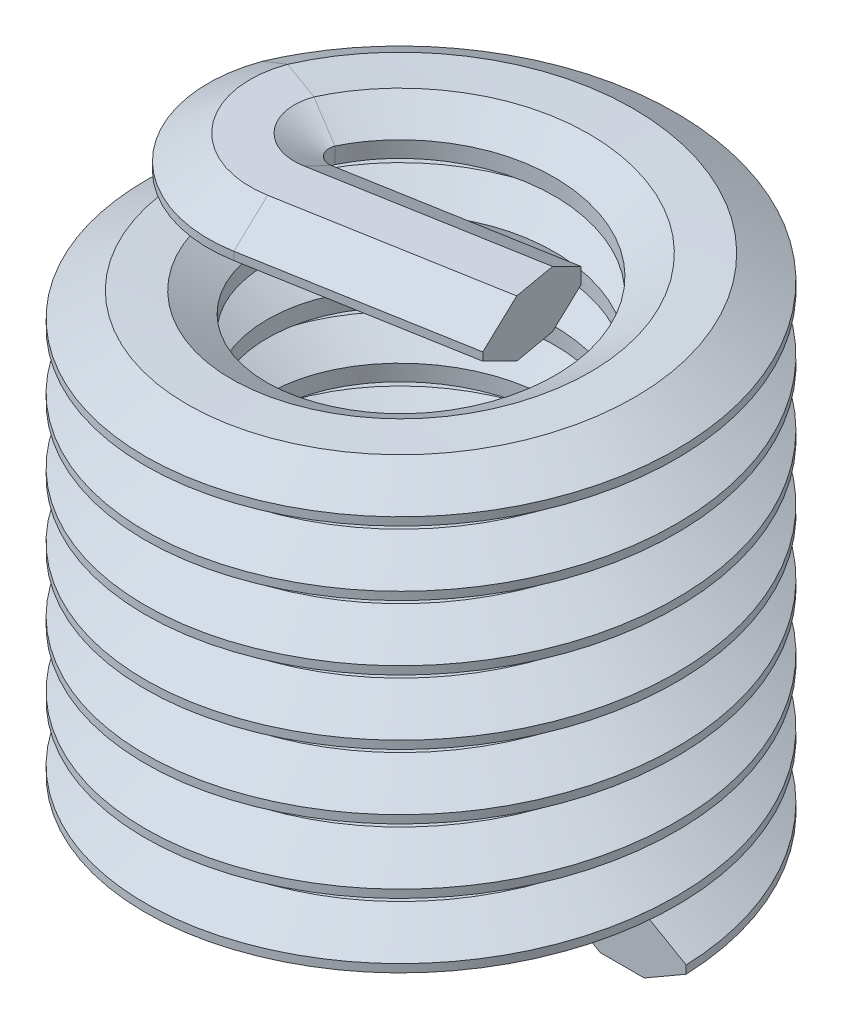
SolidWorks part; units mm, degrees
ref_plane "Front Plane" through (0, 0, 0) normal (0, 0, 1) x (1, 0, 0)
ref_plane "Top Plane" through (0, 0, 0) normal (0, 1, 0) x (1, 0, 0)
ref_plane "Right Plane" through (0, 0, 0) normal (1, 0, 0) x (0, 0, -1)
sketch "Sketch1" plane through (0, 0, 0) normal (0, 0, 1) x (-1, 0, 0)
  line L0 (0, 0) -> (0, 9.525) construction
  line L1 (-0.909, 0) -> (-1.2987, 0.225) construction
  line L2 (-1.509, 0.225) -> (-1.8987, 0) construction
  line L3 (-1.8987, 0) -> (-1.509, -0.225) construction
  line L4 (-1.2987, -0.225) -> (-0.909, 0) construction
  line L5 (-1.2987, -0.225) -> (-1.2987, 0.225) construction
  line L6 (-0.909, 0) -> (0, 0) construction
  line L8 (-1.85, -0.0281) -> (-1.5577, -0.1969)
  line L9 (-1.25, -0.1969) -> (-1.0064, -0.0563)
  line L10 (-0.9577, -0.0281) -> (-0.9577, 0.0281) construction
  line L11 (-1.0064, 0.0563) -> (-1.25, 0.1969)
  line L12 (-1.5577, 0.1969) -> (-1.85, 0.0281)
  line L13 (-0.909, 0) -> (-0.9577, 0) construction
  line L14 (-0.9577, 0) -> (-1.25, 0) construction
  line L15 (-1.5577, 0) -> (-1.85, 0) construction
  line L16 (-1.85, 0) -> (-1.8987, 0) construction
  line L17 (-1.5577, 0.1969) -> (-1.25, 0.1969)
  line L18 (-1.25, 0.1969) -> (-1.25, -0.1969) construction
  line L19 (-1.25, -0.1969) -> (-1.5577, -0.1969)
  line L20 (-1.5577, -0.1969) -> (-1.5577, 0.1969) construction
  line L21 (-1.5577, 0) -> (-1.2987, 0) construction
  line L22 (-1.2987, 0) -> (-1.25, 0) construction
  line L23 (-1.85, 0.225) -> (-1.85, -3.575) construction
  line L24 (-1.0064, -0.0563) -> (-1.0064, 0.0563)
  line L25 (-1.0064, 0) -> (-0.9577, 0) construction
  line L26 (-1.85, -0.0281) -> (-1.85, 0.0281)
  line L28 (1.85, 0.225) -> (1.85, -3.575) construction
  line L29 (-1.2987, -0.225) -> (-1.509, -0.225) construction
  line L31 (-1.509, 0.225) -> (-1.2987, 0.225) construction
sketch "Sketch2" plane through (0, 0, 0) normal (0, 1, 0) x (1, 0, 0)
  circle A0 centre (0, 0) radius 1.25
curve "Helix/Spiral1" pitch 0.45 height 3.35 turns 7.4444 parameters "Height"=3.35, "Pitch"=0.45
sweep "Sweep1" add profiles "Sketch1" path "Helix/Spiral1"
sketch "Sketch3" plane through (0, 0, 0) normal (-0.342, 0, 0.9397) x (0.9397, 0, 0.342)
  line L0 (-5.3503, 0.7863) -> (-0.909, 3.3505) construction
  line L1 (-8.4978, 7.732) -> (-0.909, 3.3505) construction
  line L2 (-0.909, 3.3505) -> (-0.909, 3.463) construction
  line L8 (-1.25, 3.1536) -> (-1.0064, 3.2943)
  line L9 (-1.0064, 3.2943) -> (-1.0064, 3.4068)
  line L10 (-1.0064, 3.4068) -> (-1.25, 3.5474)
  line L12 (-1.5577, 3.5474) -> (-1.85, 3.3786)
  line L13 (-1.85, 3.3786) -> (-1.85, 3.3224)
  line L14 (-1.85, 3.3224) -> (-1.5577, 3.1536)
  line L16 (-1.25, 3.1536) -> (-1.0064, 3.2943)
  line L17 (-1.0064, 3.2943) -> (-1.0064, 3.4068)
  line L18 (-1.0064, 3.4068) -> (-1.25, 3.5474)
  line L20 (-1.5577, 3.5474) -> (-1.85, 3.3786)
  line L21 (-1.85, 3.3786) -> (-1.85, 3.3224)
  line L22 (-1.85, 3.3224) -> (-1.5577, 3.1536)
  line L23 (-1.25, 3.5474) -> (-1.5577, 3.5474)
  line L24 (-1.25, 3.5474) -> (-1.5577, 3.5474)
  line L25 (-1.5577, 3.1536) -> (-1.25, 3.1536)
  line L26 (-1.5577, 3.1536) -> (-1.25, 3.1536)
  dimension "D1" = 0
revolve "Revolve1" add sketch "Sketch3" angle 120 about L2
sketch "Sketch4" plane through (-0.7752, 0, 0.1367) normal (0.9848, 0, -0.1737) x (-0.1737, 0, -0.9848)
  line L8 (-0.1942, 3.1536) -> (0.1135, 3.1536)
  line L9 (0.1135, 3.1536) -> (0.3571, 3.2943)
  line L10 (0.3571, 3.2943) -> (0.3571, 3.4068)
  line L11 (0.3571, 3.4068) -> (0.1135, 3.5474)
  line L12 (-0.1942, 3.1536) -> (0.1135, 3.1536)
  line L13 (-0.1942, 3.5474) -> (-0.4865, 3.3786)
  line L14 (-0.4865, 3.3786) -> (-0.4865, 3.3224)
  line L15 (-0.4865, 3.3224) -> (-0.1942, 3.1536)
  line L17 (0.1135, 3.1536) -> (0.3571, 3.2943)
  line L18 (0.3571, 3.2943) -> (0.3571, 3.4068)
  line L19 (0.3571, 3.4068) -> (0.1135, 3.5474)
  line L21 (-0.1942, 3.5474) -> (-0.4865, 3.3786)
  line L22 (-0.4865, 3.3786) -> (-0.4865, 3.3224)
  line L23 (-0.4865, 3.3224) -> (-0.1942, 3.1536)
  spline S4 degree 1 poles (2000.1056, 3.5431) (-2000.1872, 3.5517) knots -6499.464709 -6499.464709 6500.467925 6500.467925 only from (0.1135, 3.5474) to (-0.1942, 3.5474)
  spline S5 degree 1 poles (0.1135, 3.5474) (-0.1942, 3.5474) knots 0 0 1 1
  dimension "D1" = 0
extrude "Extrude1" add sketch "Sketch4" along normal blind 1.5
equation "\"D3@Sketch1\" = \"Pitch@Helix/Spiral1\""
equation "\"D4@Sketch1\" = \"D3@Sketch1\"  * 1 / 8"
equation "\"D1@Extrude1\" = \"Thread Size@Sketch1\" * 0.6"
equation "\"Height@Helix/Spiral1\" = \"Installed Length@Sketch1\" - \"Pitch@Helix/Spiral1\""
